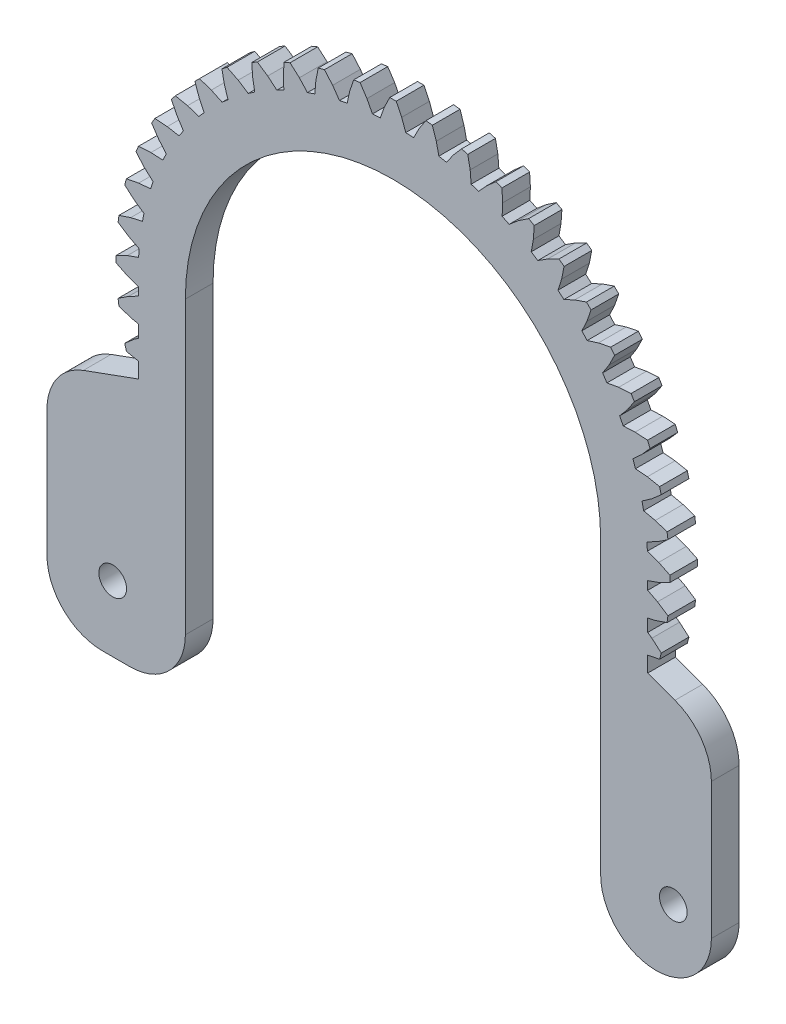
SolidWorks part; units mm, degrees
material "Delrin 2700 NC010, Low Viscosity Acetal Copolymer (SS)"
ref_plane "Front Plane" through (0, 0, 0) normal (0, 0, 1) x (1, 0, 0)
ref_plane "Top Plane" through (0, 0, 0) normal (0, 1, 0) x (1, 0, 0)
ref_plane "Right Plane" through (0, 0, 0) normal (1, 0, 0) x (0, 0, -1)
sketch "Sketch1" plane through (0, 0, 0) normal (0, 0, 1) x (1, 0, 0)
  line L0 (83.8835, 67.191) -> (85.5092, 66.6061)
  line L1 (85.5092, 66.6061) -> (87.1271, 65.8138)
  line L2 (87.1271, 65.8138) -> (87.1271, 64.8854)
  line L3 (87.1271, 64.8854) -> (85.5092, 64.0931)
  line L4 (85.5092, 64.0931) -> (83.8835, 63.5083)
  line L5 (83.8835, 63.5083) -> (83.8095, 62.3776)
  line L6 (83.8095, 62.3776) -> (85.3448, 61.5855)
  line L7 (85.3448, 61.5855) -> (86.8456, 60.5888)
  line L8 (86.8456, 60.5888) -> (86.7243, 59.6683)
  line L9 (86.7243, 59.6683) -> (85.0168, 59.094)
  line L10 (85.0168, 59.094) -> (83.3288, 58.7263)
  line L11 (83.3288, 58.7263) -> (83.1077, 57.615)
  line L12 (83.1077, 57.615) -> (84.5266, 56.6293)
  line L13 (84.5266, 56.6293) -> (85.8844, 55.4453)
  line L14 (85.8844, 55.4453) -> (85.6441, 54.5485)
  line L15 (85.6441, 54.5485) -> (83.8761, 54.202)
  line L16 (83.8761, 54.202) -> (82.1545, 54.0577)
  line L17 (82.1545, 54.0577) -> (81.7903, 52.9848)
  line L18 (81.7903, 52.9848) -> (83.0684, 51.8222)
  line L19 (83.0684, 51.8222) -> (84.26, 50.4711)
  line L20 (84.26, 50.4711) -> (83.9048, 49.6134)
  line L21 (83.9048, 49.6134) -> (82.1066, 49.5006)
  line L22 (82.1066, 49.5006) -> (80.3809, 49.5823)
  line L23 (80.3809, 49.5823) -> (79.8799, 48.5661)
  line L24 (79.8799, 48.5661) -> (80.9952, 47.2468)
  line L25 (80.9952, 47.2468) -> (82.0003, 45.7516)
  line L26 (82.0003, 45.7516) -> (81.5361, 44.9476)
  line L27 (81.5361, 44.9476) -> (79.7387, 45.0704)
  line L28 (79.7387, 45.0704) -> (78.0384, 45.3766)
  line L29 (78.0384, 45.3766) -> (77.4089, 44.4346)
  line L30 (77.4089, 44.4346) -> (78.3426, 42.9809)
  line L31 (78.3426, 42.9809) -> (79.1439, 41.3674)
  line L32 (79.1439, 41.3674) -> (78.5788, 40.6309)
  line L33 (78.5788, 40.6309) -> (76.8128, 40.9873)
  line L34 (76.8128, 40.9873) -> (75.167, 41.5128)
  line L35 (75.167, 41.5128) -> (74.4199, 40.6609)
  line L36 (74.4199, 40.6609) -> (75.1558, 39.0979)
  line L37 (75.1558, 39.0979) -> (75.7397, 37.3936)
  line L38 (75.7397, 37.3936) -> (75.0832, 36.737)
  line L39 (75.0832, 36.737) -> (73.3788, 37.3209)
  line L40 (73.3788, 37.3209) -> (71.8158, 38.0569)
  line L41 (71.8158, 38.0569) -> (70.9639, 37.3097)
  line L42 (70.9639, 37.3097) -> (71.4895, 35.6639)
  line L43 (71.4895, 35.6639) -> (71.8459, 33.898)
  line L44 (71.8459, 33.898) -> (71.1093, 33.3328)
  line L45 (71.1093, 33.3328) -> (69.4958, 34.1341)
  line L46 (69.4958, 34.1341) -> (68.0421, 35.0679)
  line L47 (68.0421, 35.0679) -> (67.1001, 34.4384)
  line L48 (67.1001, 34.4384) -> (67.4064, 32.738)
  line L49 (67.4064, 32.738) -> (67.5292, 30.9407)
  line L50 (67.5292, 30.9407) -> (66.7251, 30.4764)
  line L51 (66.7251, 30.4764) -> (65.23, 31.4815)
  line L52 (65.23, 31.4815) -> (63.9107, 32.5969)
  line L53 (63.9107, 32.5969) -> (62.8945, 32.0958)
  line L54 (62.8945, 32.0958) -> (62.9762, 30.3701)
  line L55 (62.9762, 30.3701) -> (62.8633, 28.572)
  line L56 (62.8633, 28.572) -> (62.0056, 28.2167)
  line L57 (62.0056, 28.2167) -> (60.6545, 29.4083)
  line L58 (60.6545, 29.4083) -> (59.4919, 30.6864)
  line L59 (59.4919, 30.6864) -> (58.419, 30.3222)
  line L60 (58.419, 30.3222) -> (58.2748, 28.6006)
  line L61 (58.2748, 28.6006) -> (57.9283, 26.8327)
  line L62 (57.9283, 26.8327) -> (57.0315, 26.5924)
  line L63 (57.0315, 26.5924) -> (55.8474, 27.9502)
  line L64 (55.8474, 27.9502) -> (54.8618, 29.369)
  line L65 (54.8618, 29.369) -> (53.7504, 29.1479)
  line L66 (53.7504, 29.1479) -> (53.3827, 27.4599)
  line L67 (53.3827, 27.4599) -> (52.8084, 25.7524)
  line L68 (52.8084, 25.7524) -> (51.888, 25.6311)
  line L69 (51.888, 25.6311) -> (50.8913, 27.1319)
  line L70 (50.8913, 27.1319) -> (50.0992, 28.6672)
  line L71 (50.0992, 28.6672) -> (48.9685, 28.5932)
  line L72 (48.9685, 28.5932) -> (48.3836, 26.9675)
  line L73 (48.3836, 26.9675) -> (47.5914, 25.3496)
  line L74 (47.5914, 25.3496) -> (46.6629, 25.3496)
  line L75 (46.6629, 25.3496) -> (45.8707, 26.9675)
  line L76 (45.8707, 26.9675) -> (45.2858, 28.5932)
  line L77 (45.2858, 28.5932) -> (44.1551, 28.6672)
  line L78 (44.1551, 28.6672) -> (43.363, 27.1319)
  line L79 (43.363, 27.1319) -> (42.3663, 25.6311)
  line L80 (42.3663, 25.6311) -> (41.4459, 25.7524)
  line L81 (41.4459, 25.7524) -> (40.8715, 27.4599)
  line L82 (40.8715, 27.4599) -> (40.5038, 29.1479)
  line L83 (40.5038, 29.1479) -> (39.3925, 29.369)
  line L84 (39.3925, 29.369) -> (38.4068, 27.9502)
  line L85 (38.4068, 27.9502) -> (37.2228, 26.5924)
  line L86 (37.2228, 26.5924) -> (36.326, 26.8327)
  line L87 (36.326, 26.8327) -> (35.9795, 28.6006)
  line L88 (35.9795, 28.6006) -> (35.8352, 30.3222)
  line L89 (35.8352, 30.3222) -> (34.7624, 30.6864)
  line L90 (34.7624, 30.6864) -> (33.5998, 29.4083)
  line L91 (33.5998, 29.4083) -> (32.2487, 28.2167)
  line L92 (32.2487, 28.2167) -> (31.3909, 28.572)
  line L93 (31.3909, 28.572) -> (31.2781, 30.3701)
  line L94 (31.2781, 30.3701) -> (31.3598, 32.0958)
  line L95 (31.3598, 32.0958) -> (30.3436, 32.5969)
  line L96 (30.3436, 32.5969) -> (29.0243, 31.4815)
  line L97 (29.0243, 31.4815) -> (27.5292, 30.4764)
  line L98 (27.5292, 30.4764) -> (26.7251, 30.9407)
  line L99 (26.7251, 30.9407) -> (26.8479, 32.738)
  line L100 (26.8479, 32.738) -> (27.1541, 34.4384)
  line L101 (27.1541, 34.4384) -> (26.2121, 35.0679)
  line L102 (26.2121, 35.0679) -> (24.7585, 34.1341)
  line L103 (24.7585, 34.1341) -> (23.1449, 33.3328)
  line L104 (23.1449, 33.3328) -> (22.4084, 33.898)
  line L105 (22.4084, 33.898) -> (22.7648, 35.6639)
  line L106 (22.7648, 35.6639) -> (23.2904, 37.3097)
  line L107 (23.2904, 37.3097) -> (22.4384, 38.0569)
  line L108 (22.4384, 38.0569) -> (20.8754, 37.3209)
  line L109 (20.8754, 37.3209) -> (19.1711, 36.737)
  line L110 (19.1711, 36.737) -> (18.5146, 37.3936)
  line L111 (18.5146, 37.3936) -> (19.0984, 39.0979)
  line L112 (19.0984, 39.0979) -> (19.8344, 40.6609)
  line L113 (19.8344, 40.6609) -> (19.0872, 41.5128)
  line L114 (19.0872, 41.5128) -> (17.4414, 40.9873)
  line L115 (17.4414, 40.9873) -> (15.6755, 40.6309)
  line L116 (15.6755, 40.6309) -> (15.1103, 41.3674)
  line L117 (15.1103, 41.3674) -> (15.9116, 42.9809)
  line L118 (15.9116, 42.9809) -> (16.8454, 44.4346)
  line L119 (16.8454, 44.4346) -> (16.2159, 45.3766)
  line L120 (16.2159, 45.3766) -> (14.5155, 45.0704)
  line L121 (14.5155, 45.0704) -> (12.7182, 44.9476)
  line L122 (12.7182, 44.9476) -> (12.2539, 45.7516)
  line L123 (12.2539, 45.7516) -> (13.2591, 47.2468)
  line L124 (13.2591, 47.2468) -> (14.3744, 48.5661)
  line L125 (14.3744, 48.5661) -> (13.8733, 49.5823)
  line L126 (13.8733, 49.5823) -> (12.1476, 49.5006)
  line L127 (12.1476, 49.5006) -> (10.3495, 49.6134)
  line L128 (10.3495, 49.6134) -> (9.9942, 50.4711)
  line L129 (9.9942, 50.4711) -> (11.1858, 51.8222)
  line L130 (11.1858, 51.8222) -> (12.4639, 52.9848)
  line L131 (12.4639, 52.9848) -> (12.0997, 54.0577)
  line L132 (12.0997, 54.0577) -> (10.3781, 54.202)
  line L133 (10.3781, 54.202) -> (8.6102, 54.5485)
  line L134 (8.6102, 54.5485) -> (8.3699, 55.4453)
  line L135 (8.3699, 55.4453) -> (9.7277, 56.6293)
  line L136 (9.7277, 56.6293) -> (11.1465, 57.615)
  line L137 (11.1465, 57.615) -> (10.9255, 58.7263)
  line L138 (10.9255, 58.7263) -> (9.2374, 59.094)
  line L139 (9.2374, 59.094) -> (7.5299, 59.6683)
  line L140 (7.5299, 59.6683) -> (7.4086, 60.5888)
  line L141 (7.4086, 60.5888) -> (8.9094, 61.5855)
  line L142 (8.9094, 61.5855) -> (10.4448, 62.3776)
  line L143 (10.4448, 62.3776) -> (10.3707, 63.5083)
  line L144 (10.3707, 63.5083) -> (8.745, 64.0931)
  line L145 (8.745, 64.0931) -> (7.1271, 64.8854)
  line L146 (7.1271, 64.8854) -> (7.1271, 65.8138)
  line L147 (7.1271, 65.8138) -> (8.745, 66.6061)
  line L148 (8.745, 66.6061) -> (10.3707, 67.191)
  line L149 (10.3707, 67.191) -> (10.4448, 68.3216)
  line L150 (10.4448, 68.3216) -> (8.9094, 69.1138)
  line L151 (8.9094, 69.1138) -> (7.4086, 70.1105)
  line L152 (7.4086, 70.1105) -> (7.5299, 71.0309)
  line L153 (7.5299, 71.0309) -> (9.2374, 71.6052)
  line L154 (9.2374, 71.6052) -> (10.9255, 71.9729)
  line L155 (10.9255, 71.9729) -> (11.1465, 73.0842)
  line L156 (11.1465, 73.0842) -> (9.7277, 74.0699)
  line L157 (9.7277, 74.0699) -> (8.3699, 75.254)
  line L158 (8.3699, 75.254) -> (8.6102, 76.1508)
  line L159 (8.6102, 76.1508) -> (10.3781, 76.4973)
  line L160 (10.3781, 76.4973) -> (12.0997, 76.6415)
  line L161 (12.0997, 76.6415) -> (12.4639, 77.7144)
  line L162 (12.4639, 77.7144) -> (11.1858, 78.877)
  line L163 (11.1858, 78.877) -> (9.9942, 80.2281)
  line L164 (9.9942, 80.2281) -> (10.3495, 81.0858)
  line L165 (10.3495, 81.0858) -> (12.1476, 81.1987)
  line L166 (12.1476, 81.1987) -> (13.8733, 81.117)
  line L167 (13.8733, 81.117) -> (14.3744, 82.1332)
  line L168 (14.3744, 82.1332) -> (13.2591, 83.4525)
  line L169 (13.2591, 83.4525) -> (12.2539, 84.9476)
  line L170 (12.2539, 84.9476) -> (12.7182, 85.7516)
  line L171 (12.7182, 85.7516) -> (14.5155, 85.6289)
  line L172 (14.5155, 85.6289) -> (16.2159, 85.3226)
  line L173 (16.2159, 85.3226) -> (16.8454, 86.2646)
  line L174 (16.8454, 86.2646) -> (15.9116, 87.7183)
  line L175 (15.9116, 87.7183) -> (15.1103, 89.3318)
  line L176 (15.1103, 89.3318) -> (15.6755, 90.0684)
  line L177 (15.6755, 90.0684) -> (17.4414, 89.712)
  line L178 (17.4414, 89.712) -> (19.0872, 89.1864)
  line L179 (19.0872, 89.1864) -> (19.8344, 90.0383)
  line L180 (19.8344, 90.0383) -> (19.0984, 91.6013)
  line L181 (19.0984, 91.6013) -> (18.5146, 93.3057)
  line L182 (18.5146, 93.3057) -> (19.1711, 93.9622)
  line L183 (19.1711, 93.9622) -> (20.8754, 93.3783)
  line L184 (20.8754, 93.3783) -> (22.4384, 92.6424)
  line L185 (22.4384, 92.6424) -> (23.2904, 93.3895)
  line L186 (23.2904, 93.3895) -> (22.7648, 95.0353)
  line L187 (22.7648, 95.0353) -> (22.4084, 96.8013)
  line L188 (22.4084, 96.8013) -> (23.1449, 97.3664)
  line L189 (23.1449, 97.3664) -> (24.7585, 96.5651)
  line L190 (24.7585, 96.5651) -> (26.2121, 95.6314)
  line L191 (26.2121, 95.6314) -> (27.1541, 96.2609)
  line L192 (27.1541, 96.2609) -> (26.8479, 97.9612)
  line L193 (26.8479, 97.9612) -> (26.7251, 99.7586)
  line L194 (26.7251, 99.7586) -> (27.5292, 100.2228)
  line L195 (27.5292, 100.2228) -> (29.0243, 99.2177)
  line L196 (29.0243, 99.2177) -> (30.3436, 98.1023)
  line L197 (30.3436, 98.1023) -> (31.3598, 98.6034)
  line L198 (31.3598, 98.6034) -> (31.2781, 100.3291)
  line L199 (31.2781, 100.3291) -> (31.3909, 102.1272)
  line L200 (31.3909, 102.1272) -> (32.2487, 102.4825)
  line L201 (32.2487, 102.4825) -> (33.5998, 101.2909)
  line L202 (33.5998, 101.2909) -> (34.7624, 100.0128)
  line L203 (34.7624, 100.0128) -> (35.8352, 100.377)
  line L204 (35.8352, 100.377) -> (35.9795, 102.0986)
  line L205 (35.9795, 102.0986) -> (36.326, 103.8666)
  line L206 (36.326, 103.8666) -> (37.2228, 104.1068)
  line L207 (37.2228, 104.1068) -> (38.4068, 102.7491)
  line L208 (38.4068, 102.7491) -> (39.3925, 101.3302)
  line L209 (39.3925, 101.3302) -> (40.5038, 101.5513)
  line L210 (40.5038, 101.5513) -> (40.8715, 103.2393)
  line L211 (40.8715, 103.2393) -> (41.4459, 104.9468)
  line L212 (41.4459, 104.9468) -> (42.3663, 105.0681)
  line L213 (42.3663, 105.0681) -> (43.363, 103.5673)
  line L214 (43.363, 103.5673) -> (44.1551, 102.032)
  line L215 (44.1551, 102.032) -> (45.2858, 102.106)
  line L216 (45.2858, 102.106) -> (45.8707, 103.7317)
  line L217 (45.8707, 103.7317) -> (46.6629, 105.3496)
  line L218 (46.6629, 105.3496) -> (47.5914, 105.3496)
  line L219 (47.5914, 105.3496) -> (48.3836, 103.7317)
  line L220 (48.3836, 103.7317) -> (48.9685, 102.106)
  line L221 (48.9685, 102.106) -> (50.0992, 102.032)
  line L222 (50.0992, 102.032) -> (50.8913, 103.5673)
  line L223 (50.8913, 103.5673) -> (51.888, 105.0681)
  line L224 (51.888, 105.0681) -> (52.8084, 104.9468)
  line L225 (52.8084, 104.9468) -> (53.3827, 103.2393)
  line L226 (53.3827, 103.2393) -> (53.7504, 101.5513)
  line L227 (53.7504, 101.5513) -> (54.8618, 101.3302)
  line L228 (54.8618, 101.3302) -> (55.8474, 102.7491)
  line L229 (55.8474, 102.7491) -> (57.0315, 104.1068)
  line L230 (57.0315, 104.1068) -> (57.9283, 103.8666)
  line L231 (57.9283, 103.8666) -> (58.2748, 102.0986)
  line L232 (58.2748, 102.0986) -> (58.419, 100.377)
  line L233 (58.419, 100.377) -> (59.4919, 100.0128)
  line L234 (59.4919, 100.0128) -> (60.6545, 101.2909)
  line L235 (60.6545, 101.2909) -> (62.0056, 102.4825)
  line L236 (62.0056, 102.4825) -> (62.8633, 102.1272)
  line L237 (62.8633, 102.1272) -> (62.9762, 100.3291)
  line L238 (62.9762, 100.3291) -> (62.8945, 98.6034)
  line L239 (62.8945, 98.6034) -> (63.9107, 98.1023)
  line L240 (63.9107, 98.1023) -> (65.23, 99.2177)
  line L241 (65.23, 99.2177) -> (66.7251, 100.2228)
  line L242 (66.7251, 100.2228) -> (67.5292, 99.7586)
  line L243 (67.5292, 99.7586) -> (67.4064, 97.9612)
  line L244 (67.4064, 97.9612) -> (67.1001, 96.2609)
  line L245 (67.1001, 96.2609) -> (68.0421, 95.6314)
  line L246 (68.0421, 95.6314) -> (69.4958, 96.5651)
  line L247 (69.4958, 96.5651) -> (71.1093, 97.3664)
  line L248 (71.1093, 97.3664) -> (71.8459, 96.8013)
  line L249 (71.8459, 96.8013) -> (71.4895, 95.0353)
  line L250 (71.4895, 95.0353) -> (70.9639, 93.3895)
  line L251 (70.9639, 93.3895) -> (71.8158, 92.6424)
  line L252 (71.8158, 92.6424) -> (73.3788, 93.3783)
  line L253 (73.3788, 93.3783) -> (75.0832, 93.9622)
  line L254 (75.0832, 93.9622) -> (75.7397, 93.3057)
  line L255 (75.7397, 93.3057) -> (75.1558, 91.6013)
  line L256 (75.1558, 91.6013) -> (74.4199, 90.0383)
  line L257 (74.4199, 90.0383) -> (75.167, 89.1864)
  line L258 (75.167, 89.1864) -> (76.8128, 89.712)
  line L259 (76.8128, 89.712) -> (78.5788, 90.0684)
  line L260 (78.5788, 90.0684) -> (79.1439, 89.3318)
  line L261 (79.1439, 89.3318) -> (78.3426, 87.7183)
  line L262 (78.3426, 87.7183) -> (77.4089, 86.2646)
  line L263 (77.4089, 86.2646) -> (78.0384, 85.3226)
  line L264 (78.0384, 85.3226) -> (79.7387, 85.6289)
  line L265 (79.7387, 85.6289) -> (81.5361, 85.7516)
  line L266 (81.5361, 85.7516) -> (82.0003, 84.9476)
  line L267 (82.0003, 84.9476) -> (80.9952, 83.4525)
  line L268 (80.9952, 83.4525) -> (79.8799, 82.1332)
  line L269 (79.8799, 82.1332) -> (80.3809, 81.117)
  line L270 (80.3809, 81.117) -> (82.1066, 81.1987)
  line L271 (82.1066, 81.1987) -> (83.9048, 81.0858)
  line L272 (83.9048, 81.0858) -> (84.26, 80.2281)
  line L273 (84.26, 80.2281) -> (83.0684, 78.877)
  line L274 (83.0684, 78.877) -> (81.7903, 77.7144)
  line L275 (81.7903, 77.7144) -> (82.1545, 76.6415)
  line L276 (82.1545, 76.6415) -> (83.8761, 76.4973)
  line L277 (83.8761, 76.4973) -> (85.6441, 76.1508)
  line L278 (85.6441, 76.1508) -> (85.8844, 75.254)
  line L279 (85.8844, 75.254) -> (84.5266, 74.0699)
  line L280 (84.5266, 74.0699) -> (83.1077, 73.0842)
  line L281 (83.1077, 73.0842) -> (83.3288, 71.9729)
  line L282 (83.3288, 71.9729) -> (85.0168, 71.6052)
  line L283 (85.0168, 71.6052) -> (86.7243, 71.0309)
  line L284 (86.7243, 71.0309) -> (86.8456, 70.1105)
  line L285 (86.8456, 70.1105) -> (85.3448, 69.1138)
  line L286 (85.3448, 69.1138) -> (83.8095, 68.3216)
  line L287 (83.8095, 68.3216) -> (83.8835, 67.191)
  line L288 (47.1271, 105.3496) -> (47.1271, 25.3496) construction
  line L289 (7.1271, 65.3496) -> (87.1271, 65.3496) construction
  point P292 (47.1271, 65.3496)
sketch "Sketch2" plane through (0, 0, 0) normal (0, 0, 1) x (1, 0, 0)
  line L0 (-2.8729, 47.1511) -> (10.3271, 51.9555)
  line L1 (47.1271, 65.3496) -> (97.1271, 65.3496) construction
  line L2 (47.1271, 65.3496) -> (47.1271, 15.3496) construction
  line L3 (83.9271, 51.9555) -> (47.1271, 65.3496) construction
  line L4 (83.9271, 51.9555) -> (83.9271, 65.3496)
  line L5 (97.1271, 47.1511) -> (97.1271, 15.3496) construction
  line L6 (47.1271, 65.3496) -> (47.1271, 15.3496) construction
  line L7 (97.1271, 15.3496) -> (-2.8729, 15.3496)
  line L8 (-2.8729, 47.1511) -> (-2.8729, 15.3496)
  line L9 (47.1271, 65.3496) -> (97.1271, 65.3496) construction
  line L10 (7.1271, 65.3496) -> (87.1271, 65.3496) construction
  line L11 (97.1271, 47.1511) -> (83.9271, 51.9555)
  line L12 (93.1271, 48.607) -> (93.1271, 15.3496)
  line L14 (10.3271, 51.9555) -> (10.3271, 65.3496)
  line L15 (10.3271, 65.3496) -> (83.9271, 65.3496)
  line L16 (10.3271, 51.9555) -> (47.1271, 65.3496) construction
  dimension "D1" = 100
  dimension "D2" = 50
  dimension "D3" = 20
  dimension "D4" = 4
  dimension "D5" = 36.8
sketch "Sketch3" plane through (0, 0, 0) normal (0, 0, 1) x (1, 0, 0)
  line L0 (6.6271, 24.8496) -> (-2.8729, 24.8496) construction
  line L1 (-2.8729, 47.1511) -> (-2.8729, 15.3496) construction
  line L2 (6.6271, 24.8496) -> (6.6271, 15.3496) construction
  line L3 (97.1271, 15.3496) -> (-2.8729, 15.3496) construction
  line L4 (47.1271, 65.3496) -> (47.1271, 15.3496) construction
  line L5 (7.1271, 65.3496) -> (87.1271, 65.3496) construction
  line L6 (47.1271, 65.3496) -> (97.1271, 65.3496) construction
  circle A0 centre (6.6271, 24.8496) radius 2
  circle A1 centre (87.6271, 24.8496) radius 2
  dimension "D1" = 4
  dimension "D2" = 81
sketch "Sketch4" plane through (0, 0, 0) normal (0, 0, 1) x (1, 0, 0)
  circle A0 centre (47.1271, 65.3496) radius 30
  dimension "D1" = 60
extrude "Boss-Extrude1" add sketch "Sketch1" along normal blind 4
extrude "Boss-Extrude2" add sketch "Sketch2" along normal blind 4 contours L15 L14 L0 L8 L7 L12 L11 L4 region at (45.7249, 39.0089, 0)
extrude "Cut-Extrude1" cut sketch "Sketch3" along normal up to next
extrude "Cut-Extrude2" cut sketch "Sketch4" along normal up to next
sketch "Sketch5" plane through (0, 0, 0) normal (0, 0, 1) x (1, 0, 0)
  line L0 (77.1271, 65.3496) -> (77.1271, 15.3496)
  line L2 (17.1271, 65.3496) -> (17.1271, 15.3496)
  line L3 (17.1271, 15.3496) -> (77.1271, 15.3496)
  line L4 (17.1271, 65.3496) -> (77.1271, 65.3496)
  line L5 (93.1271, 15.3496) -> (-2.8729, 15.3496) construction
  circle A0 centre (47.1271, 65.3496) radius 30 construction
  dimension "D1" = 60
extrude "Cut-Extrude3" cut sketch "Sketch5" along normal up to next
fillet "Fillet1" radius 8 6 edges at (77.1271, 15.3496, 2) (17.1271, 15.3496, 2) (-2.8729, 15.3496, 2) (-2.8729, 47.1511, 2) (93.1271, 15.3496, 2) (93.1271, 48.607, 2)
